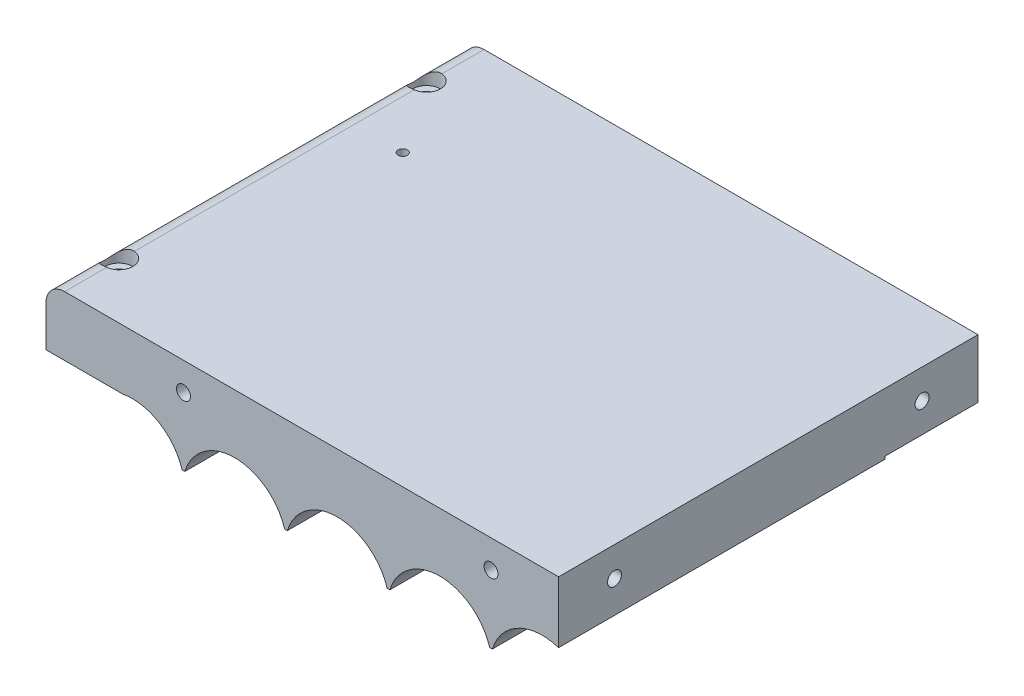
SolidWorks part; units mm, degrees
ref_plane "前视基准面" through (0, 0, 0) normal (0, 0, 1) x (1, 0, 0)
ref_plane "上视基准面" through (0, 0, 0) normal (0, 1, 0) x (1, 0, 0)
ref_plane "右视基准面" through (0, 0, 0) normal (1, 0, 0) x (0, 0, -1)
other "Configuration Table"
sketch "草图1" plane through (0, 0, 0) normal (0, 1, 0) x (1, 0, 0)
  line L1 (0, 0) -> (110, 0)
  line L2 (0, 0) -> (0, 70)
  line L3 (0, 70) -> (110, 70)
  line L4 (110, 0) -> (110, 70)
  dimension "D1" = 70
  dimension "D2" = 110
extrude "凸台-拉伸1" add sketch "草图1" along normal blind 5
sketch "草图2" plane through (0, 0, -70) normal (0, 0, -1) x (-1, 0, 0)
  line L0 (-110, 0) -> (-110, -8.3803)
  line L1 (0, 0) -> (0, -7.8087)
  line L2 (0, -7.8087) -> (-18.5, -7.8087)
  line L3 (-29, -15.53) -> (-96, -15.53)
  circle A0 centre (-18.5, -18.8087) radius 11 construction
  circle A1 centre (-40.5, -18.8087) radius 11 construction
  circle A2 centre (-62.5, -18.8087) radius 11 construction
  circle A3 centre (-84.5, -18.8087) radius 11 construction
  circle A4 centre (-106.5, -18.8087) radius 11 construction
  circle A5 centre (-18.5, -18.8087) radius 11
  circle A6 centre (-40.5, -18.8087) radius 11
  circle A7 centre (-62.5, -18.8087) radius 11
  circle A8 centre (-84.5, -18.8087) radius 11
  circle A9 centre (-106.5, -18.8087) radius 11
  line M2 (-110, 0) -> (0, 0)
  dimension "D1" = 67
extrude "凸台-拉伸2" add sketch "草图2" against normal up to surface (70 mm away) contours A9 L3 A8 A7 A6 A5 L2 L1 L0 M2 region at (56.4687, -5.0993, -70) up to face at (55, 2.5, 0)
sketch "草图3" plane through (0, 0, -70) normal (0, 0, -1) x (-1, 0, 0)
  line L0 (-106.5, -18.8087) -> (-84.5, -18.8087) construction
  circle A0 centre (-106.5, -18.8087) radius 11.2
  arc A1 (-96, -15.53) -> (-110, -8.3803) centre (-106.5, -18.8087) ccw construction
  circle A2 centre (-84.5, -18.8087) radius 11.2
  circle A3 centre (-62.5, -18.8087) radius 11.2
  circle A4 centre (-40.5, -18.8087) radius 11.2
  circle A5 centre (-18.5, -18.8087) radius 11.2
  line M1 (-110, 5) -> (-110, -8.3803)
  arc M2 (-110, -8.3803) -> (-96, -15.53) centre (-106.5, -18.8087) cw
  line M3 (-96, -15.53) -> (-95, -15.53)
  arc M4 (-95, -15.53) -> (-74, -15.53) centre (-84.5, -18.8087) cw
  line M5 (-74, -15.53) -> (-73, -15.53)
  arc M6 (-73, -15.53) -> (-52, -15.53) centre (-62.5, -18.8087) cw
  line M7 (-52, -15.53) -> (-51, -15.53)
  arc M8 (-51, -15.53) -> (-30, -15.53) centre (-40.5, -18.8087) cw
  line M9 (-30, -15.53) -> (-29, -15.53)
  arc M10 (-29, -15.53) -> (-18.5, -7.8087) centre (-18.5, -18.8087) cw
  line M11 (-18.5, -7.8087) -> (0, -7.8087)
  dimension "D1" = 22.4
  dimension "D3" = 22
  dimension "D2" = 5
extrude "切除-拉伸2" cut sketch "草图3" against normal up to surface (70 mm away) contours A2 A0 M3 M2 M1 | A3 A2 A0 M5 M4 M3 | A4 A3 A2 M7 M6 M5 | A5 A4 A3 M9 M8 M7 | A5 A4 M9 M11 M10 | A5 | A4 | A3 | A0 | A2 region at (84.5, -18.9306, -70) region at (106.5732, -18.8891, -70) region at (62.5, -18.9306, -70) region at (40.5, -18.9306, -70) region at (18.4243, -18.8771, -70) up to face at (56.7895, -8.4929, 0)
sketch "草图4" plane through (0, 0, -70) normal (0, 0, -1) x (-1, 0, 0)
  line L0 (-110, 5) -> (-110, -8.1696) construction
  line L1 (0, 5) -> (-110, 5)
  line L2 (0, 5) -> (0, -7.6087)
  line L3 (-7.3, -7.6087) -> (-110, -7.6087)
  line L4 (-110, 5) -> (-110, -7.6087)
  line L6 (0, -7.8087) -> (-7.3, -7.8087)
  line L7 (0, -7.8087) -> (0, -7.6087)
  line L9 (-7.3, -7.8087) -> (-7.3, -7.6087)
  dimension "D1" = 12.6087
  dimension "D2" = 7.3
  dimension "D3" = 0.2
extrude "凸台-拉伸3" add sketch "草图4" along normal blind 20
sketch "草图5" plane through (0, 0, 0) normal (0, 0, 1) x (1, 0, 0)
  circle A2 centre (95.5, -1) radius 1.5
  circle A3 centre (29.5, -1) radius 1.5
  dimension "D1" = 3
extrude "切除-拉伸3" cut sketch "草图5" against normal blind 10 contours A2 | A3
sketch "草图6" plane through (110, 0, 0) normal (1, 0, 0) x (0, 0, -1)
  line L0 (90, -1.3043) -> (-0.0004, -1.3043) construction
  line L1 (90, 5) -> (90, -7.6087) construction
  line L2 (0, 5) -> (0, -8.1696) construction
  circle A0 centre (78, -1.3043) radius 1.5
  circle A1 centre (12, -1.3043) radius 1.5
  dimension "D3" = 3
  dimension "D1" = 12
  dimension "D2" = 12
extrude "切除-拉伸4" cut sketch "草图6" against normal blind 10
sketch "草图7" plane through (0, 5, 0) normal (0, 1, 0) x (1, 0, 0)
  line L1 (0, 90) -> (7.3, 90) construction
  line L2 (3.65, 90) -> (3.65, 0) construction
  line L3 (0, 0) -> (110, 0) construction
  circle A0 centre (3.65, 78) radius 1.5
  circle A1 centre (3.65, 12) radius 1.5
  dimension "D1" = 3
  dimension "D3" = 12
  dimension "D2" = 12
extrude "切除-拉伸5" cut sketch "草图7" against normal up to next and the other way through all contours A0 | A1 region at (3.65, 5, -78) region at (3.65, 5, -12)
sketch "草图8" plane through (0, 5, 0) normal (0, 1, 0) x (1, 0, 0)
  circle A0 centre (3.65, 12) radius 3
  circle A1 centre (3.65, 78) radius 3
  dimension "D1" = 6
extrude "切除-拉伸6" cut sketch "草图8" against normal blind 3
sketch "草图9" plane through (0, 5, 0) normal (0, 1, 0) x (1, 0, 0)
  circle A1 centre (14.442, 62.109) radius 1
extrude "切除-拉伸7" cut sketch "草图9" against normal up to next
fillet "圆角1" radius 4 1 edges at (0, 5, -45)
sketch "草图10" plane through (0, 0, -90) normal (0, 0, -1) x (-1, 0, 0)
  line L0 (-110, -1.3043) -> (-62.5, -1.3043) construction
  line L1 (-110, 5) -> (-110, -7.6087) construction
  line L2 (0, -7.8087) -> (0, 1) construction
  circle A0 centre (-62.5, -1.3043) radius 1.5
  dimension "D1" = 3
  dimension "D2" = 62.5
extrude "切除-拉伸8" cut sketch "草图10" against normal blind 10
